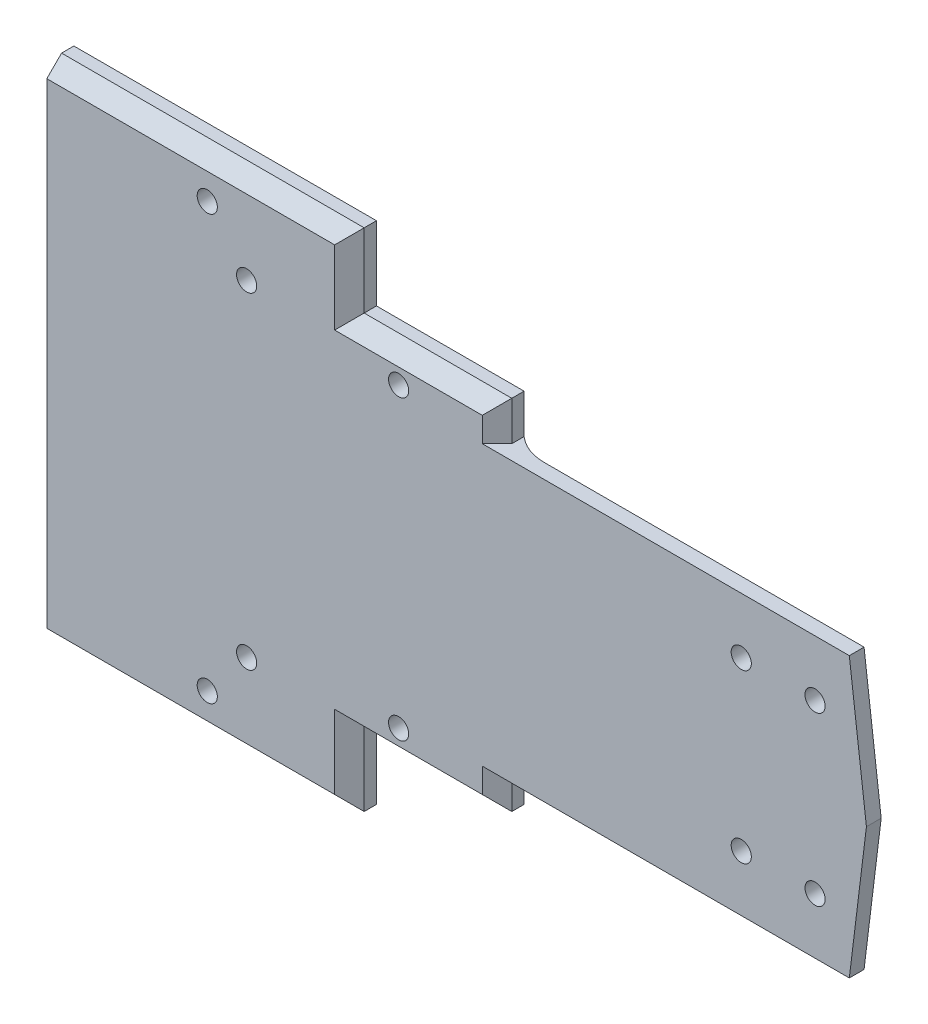
SolidWorks part; units mm, degrees
material "petg 20%"
ref_plane "Front Plane" through (0, 0, 0) normal (0, 0, 1) x (1, 0, 0)
ref_plane "Top Plane" through (0, 0, 0) normal (0, 1, 0) x (1, 0, 0)
ref_plane "Right Plane" through (0, 0, 0) normal (1, 0, 0) x (0, 0, -1)
sketch "Sketch1" plane through (0, 0, 0) normal (0, 0, 1) x (1, 0, 0)
  line L1 (-71.25, 28.37) -> (71.25, 28.37)
  line L2 (-71.25, 28.37) -> (-71.25, -28.37)
  line L3 (-71.25, -28.37) -> (71.25, -28.37)
  line L4 (71.25, 28.37) -> (71.25, -28.37)
  line L5 (-71.25, 28.37) -> (71.25, -28.37) construction
  line L6 (-71.25, -28.37) -> (71.25, 28.37) construction
  point P0 (0, 0)
  dimension "D1" = 142.5
  dimension "D2" = 56.74
extrude "Boss-Extrude1" add sketch "Sketch1" along normal blind 3
sketch "Sketch2" plane through (0, 0, 3) normal (0, 0, 1) x (1, 0, 0)
  line L0 (71.25, 0) -> (67.7716, 28.37)
  line L1 (71.25, -28.37) -> (71.25, 28.37) construction
  line L2 (71.25, 28.37) -> (-71.25, 28.37) construction
  line L3 (71.25, 0) -> (67.7716, -28.37)
  line L4 (-71.25, -28.37) -> (71.25, -28.37) construction
  line L6 (67.7716, 28.37) -> (71.25, 28.37)
  line L7 (71.25, 28.37) -> (71.25, -28.37)
  line L8 (71.25, -28.37) -> (67.7716, -28.37)
  line M3 (71.25, -28.37) -> (71.25, 28.37)
  line M4 (71.25, 28.37) -> (-71.25, 28.37)
  line M6 (-71.25, -28.37) -> (71.25, -28.37)
  dimension "D1" = 166.02
extrude "Cut-Extrude1" cut sketch "Sketch2" against normal through all contours L0 M3 M4 | L3 M3 M6 region at (70.0905, -18.9133, 3) region at (70.0905, 18.9133, 3)
sketch "Sketch3" plane through (0, 0, 3) normal (0, 0, 1) x (1, 0, 0)
  line L0 (-71.25, 28.37) -> (-71.25, -28.37)
  line L1 (-71.25, 28.37) -> (-68.825, 28.37)
  line L2 (-71.25, -28.37) -> (-68.825, -28.37)
  line L3 (-68.825, 28.37) -> (-68.825, -28.37)
  dimension "D1" = 2.425
extrude "Cut-Extrude2" cut sketch "Sketch3" against normal through all contours L0 L1 L3 L2
sketch "Sketch4" plane through (0, 0, 3) normal (0, 0, 1) x (1, 0, 0)
  line L0 (-68.825, 28.37) -> (-3.825, 28.37)
  line L1 (-68.825, 28.37) -> (-68.825, 36.37)
  line L2 (-3.825, 28.37) -> (-3.825, 36.37)
  line L3 (-68.825, 36.37) -> (-3.825, 36.37)
  line L6 (-68.825, -28.37) -> (-3.825, -28.37)
  line L7 (-68.825, -28.37) -> (-68.825, -36.37)
  line L8 (-3.825, -28.37) -> (-3.825, -36.37)
  line L9 (-68.825, -36.37) -> (-3.825, -36.37)
  line L13 (-68.825, 36.37) -> (-3.825, 36.37)
  line L14 (-68.825, 36.37) -> (-68.825, -36.37)
  line L15 (-68.825, -36.37) -> (-3.825, -36.37)
  line L16 (-3.825, 36.37) -> (-3.825, -36.37)
  dimension "D1" = 8
  dimension "D2" = 8
  dimension "D3" = 65
  dimension "D4" = 65
  dimension "D5" = 65
extrude "Boss-Extrude2" add sketch "Sketch4" against normal blind 5.5 contours L16 | L3 L1 L2 | L7 L9 L8 region at (-36.325, 32.37, 3) region at (-36.325, 0, 3) region at (-36.325, -32.37, 3)
fillet "Fillet1" radius 10 1 edges at (-3.825, 0, 0)
fillet "Fillet2" [suppressed] radius 10
sketch "Sketch5" plane through (0, 0, 3) normal (0, 0, 1) x (1, 0, 0)
  circle A0 centre (60.808, 17) radius 2.05
  circle A1 centre (60.808, -17) radius 2.05
  circle A2 centre (45.808, 17) radius 2.05
  circle A3 centre (45.808, -17) radius 2.05
  dimension "D1" = 4.1
  dimension "D3" = 4.1
  dimension "D5" = 4.1
  dimension "D6" = 4.1
  dimension "D8" = 17
  dimension "D9" = 15
  dimension "D10" = 15
  dimension "D2" = 17
  dimension "D4" = 17
  dimension "D7" = 17
extrude "Cut-Extrude3" cut sketch "Sketch5" against normal through all
sketch "Sketch6" [suppressed] plane through (0, 0, 0) normal (0, 0, -1) x (-1, 0, 0)
  circle A0 centre (-45.805, -17) radius 2.05
  circle A1 centre (-60.805, -17) radius 2.05
  circle A2 centre (-45.805, 17) radius 2.05
  circle A3 centre (-60.805, 17) radius 2.05
extrude "Cut-Extrude4" [suppressed] cut sketch "Sketch6" against normal blind 10
sketch "Sketch7" [suppressed] plane through (0, 0, 3) normal (0, 0, 1) x (1, 0, 0)
  line L1 (-68.825, 36.37) -> (-33.825, 36.37)
  line L2 (-68.825, 36.37) -> (-68.825, 51.37)
  line L3 (-68.825, 51.37) -> (-33.825, 51.37)
  line L4 (-33.825, 36.37) -> (-33.825, 51.37)
  line L5 (-68.825, -36.37) -> (-33.825, -36.37)
  line L6 (-68.825, -36.37) -> (-68.825, -51.37)
  line L7 (-68.825, -51.37) -> (-33.825, -51.37)
  line L8 (-33.825, -36.37) -> (-33.825, -51.37)
  dimension "D1" = 15
  dimension "D2" = 35
  dimension "D3" = 15
  dimension "D4" = 35
extrude "Boss-Extrude3" [suppressed] add sketch "Sketch7" against normal up to surface (4.11 mm away) up to face at (-25.4917, 0, -2.5)
sketch "Sketch9" [suppressed] plane through (0, 0, 3) normal (0, 0, 1) x (1, 0, 0)
  line L0 (-68.825, 51.37) -> (-68.825, -51.37)
  line L1 (-68.825, 51.37) -> (-95.325, 51.37)
  line L2 (-68.825, -51.37) -> (-95.325, -51.37)
  line L3 (-95.325, 51.37) -> (-95.325, -51.37)
  dimension "D1" = 26.5
extrude "Boss-Extrude4" [suppressed] add sketch "Sketch9" against normal up to surface (4.11 mm away) up to face at (-25.4917, 0, -2.5)
sketch "Sketch10" plane through (0, 0, 3) normal (0, 0, 1) x (1, 0, 0)
  line L0 (-68.825, 36.37) -> (-33.825, 36.37)
  line L2 (-33.825, 36.37) -> (-33.825, 51.37)
  line L3 (-68.825, 51.37) -> (-33.825, 51.37)
  line L4 (-68.825, 36.37) -> (-3.825, 36.37) construction
  line L5 (-68.825, -36.37) -> (-33.825, -36.37)
  line L7 (-33.825, -36.37) -> (-33.825, -51.37)
  line L8 (-68.825, -51.37) -> (-33.825, -51.37)
  line L9 (-68.825, -36.37) -> (-3.825, -36.37) construction
  line L10 (-68.825, 36.37) -> (-68.825, -36.37)
  line L11 (-68.825, 51.37) -> (-95.325, 51.37)
  line L12 (-68.825, -51.37) -> (-95.325, -51.37)
  line L13 (-95.325, 51.37) -> (-95.325, -51.37)
  dimension "D1" = 15
  dimension "D2" = 15
  dimension "D3" = 35
  dimension "D4" = 35
  dimension "D5" = 26.5
extrude "Boss-Extrude5" add sketch "Sketch10" against normal blind 5.5
chamfer "Chamfer6" distance 3 angle 45 8 edges at (-3.825, 32.37, 3) (-18.825, 36.37, 3) (-33.825, 43.87, 3) (-64.575, 51.37, 3) (-3.825, -32.37, 3) (-18.825, -36.37, 3) (-33.825, -43.87, 3) (-64.575, -51.37, 3)
chamfer "Chamfer7" [suppressed] distance 3 angle 45
sketch "Sketch11" plane through (0, 0, 3) normal (0, 0, 1) x (1, 0, 0)
  circle A1 centre (-62.7149, -43.08) radius 2.05
  circle A2 centre (-54.7149, -33.1839) radius 2.05
  circle A3 centre (-23.8214, -30.1967) radius 2.05
  dimension "D1" = 4.1
  dimension "D3" = 4.1
  dimension "D4" = 4.1
extrude "Cut-Extrude5" cut sketch "Sketch11" against normal through all
sketch "Sketch12" [suppressed] plane through (0, 0, -1.11) normal (0, 0, -1) x (-1, 0, 0)
  circle A1 centre (62.7179, 43.08) radius 2.05
  circle A2 centre (54.7179, 33.1839) radius 2.05
  circle A3 centre (23.8244, 30.1967) radius 2.05
extrude "Cut-Extrude6" [suppressed] cut sketch "Sketch12" against normal through all
ref_plane "Plane1" [suppressed] through (0, 0, 0) normal (0, 1, 0) x (1, 0, 0)
mirror "Mirror1" [suppressed] about plane through (0, 0, 0) normal (0, 1, 0)
ref_plane "Plane2" through (0, 0, 0) normal (0, 1, 0) x (1, 0, 0)
mirror "Mirror2" about plane through (0, 0, 0) normal (0, 1, 0) of "Cut-Extrude5"
